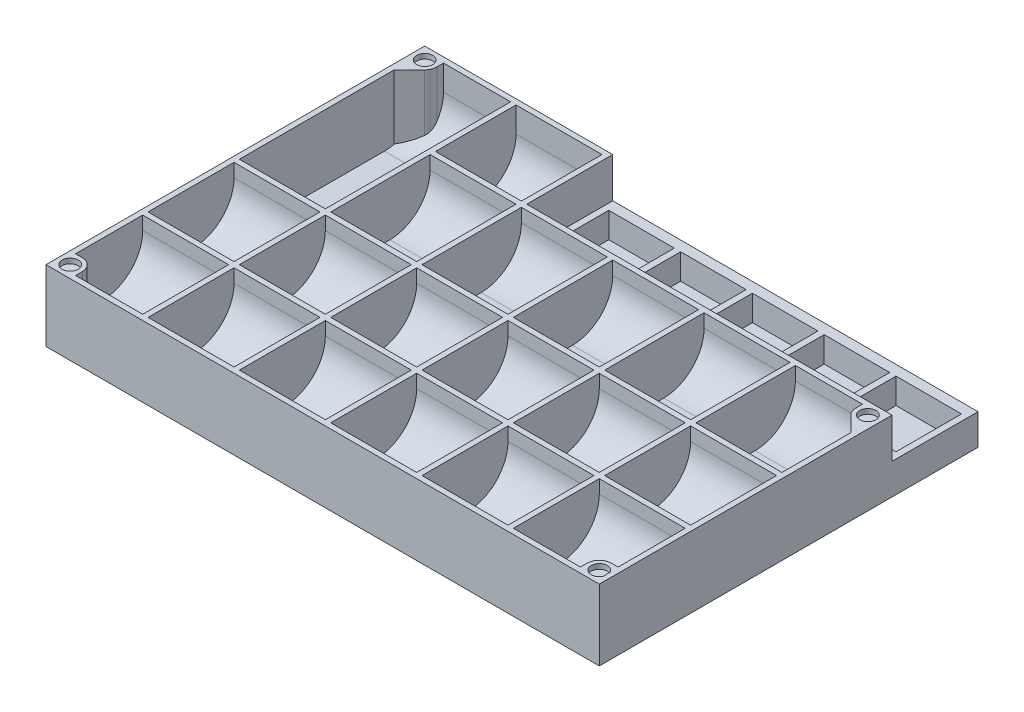
SolidWorks part; units mm, degrees
ref_plane "Front Plane" through (0, 0, 0) normal (0, 0, 1) x (1, 0, 0)
ref_plane "Top Plane" through (0, 0, 0) normal (0, 1, 0) x (1, 0, 0)
ref_plane "Right Plane" through (0, 0, 0) normal (1, 0, 0) x (0, 0, -1)
sketch "Sketch2" plane through (0, 0, 0) normal (1, 0, 0) x (0, 0, -1)
  line L0 (34, 26.4) -> (34, 32.7647)
  line L1 (0, 0) -> (141, 0)
  line L2 (0, 0) -> (0, 26.4)
  line L3 (0, 26.4) -> (141, 26.4)
  line L4 (141, 0) -> (141, 26.4)
  line L5 (2, 26.4) -> (34, 26.4)
  line L6 (2, 26.4) -> (2, 6.4)
  line L7 (2, 6.4) -> (19, 6.4)
  line L8 (34, 26.4) -> (34, 21.4)
  line L9 (36, 26.4) -> (68, 26.4)
  line L10 (36, 26.4) -> (36, 6.4)
  line L11 (36, 6.4) -> (53, 6.4)
  line L12 (68, 26.4) -> (68, 21.4)
  line L13 (70, 26.4) -> (107, 26.4)
  line L14 (70, 26.4) -> (70, 6.4)
  line L15 (70, 6.4) -> (92, 6.4)
  line L16 (107, 26.4) -> (107, 21.4)
  line L17 (109, 26.4) -> (139, 26.4)
  line L18 (109, 26.4) -> (109, 2)
  line L19 (109, 2) -> (124, 2)
  line L20 (139, 26.4) -> (139, 17)
  line L21 (70, 6.4) -> (70, 0)
  arc A0 (19, 6.4) -> (34, 21.4) centre (19, 21.4) ccw
  arc A1 (68, 21.4) -> (53, 6.4) centre (53, 21.4) cw
  arc A2 (107, 21.4) -> (92, 6.4) centre (92, 21.4) cw
  arc A3 (139, 17) -> (124, 2) centre (124, 17) cw
  dimension "D12" = 15
  dimension "D13" = 15
  dimension "D14" = 15
  dimension "D15" = 15
  dimension "D1" = 141
  dimension "D2" = 26.4
  dimension "D3" = 32
  dimension "D4" = 20
  dimension "D5" = 2
  dimension "D6" = 2
  dimension "D7" = 2
  dimension "D8" = 2
  dimension "D9" = 2
  dimension "D10" = 32
  dimension "D11" = 37
  dimension "D16" = 2
extrude "Boss-Extrude2" add sketch "Sketch2" against normal blind 2 contours L12 A1 L11 L10 L3 L8 A0 L7 L6 L2 L1 L21 L14 | L20 A3 L19 L18 L3 L16 A2 L15 L21 L1 L4 | A2 L16 L3 L14 L15 | A3 L20 L3 L18 L19 | A1 L12 L3 L10 L11 | L7 A0 L8 L3 L6 region at (0, 13.2, -0.7481) region at (0, 5.8938, -106.3105) region at (0, 16.8642, -87.4425) region at (0, 16.9426, -16.9678) region at (0, 14.825, -123.1773) region at (0, 16.9426, -50.9678)
extrude "Boss-Extrude3" add sketch "Sketch2<5>" against normal blind 34 contours L12 A1 L11 L10 L3 L8 A0 L7 L6 L2 L1 L21 L14 region at (0, 13.2, -0.7481)
sketch "Sketch2<5>" plane through (0, 0, 0) normal (1, 0, 0) x (0, 0, -1) same geometry as "Sketch2"
extrude "Boss-Extrude5" add sketch "Sketch2<9>" along normal blind 32 contours L12 A1 L11 L10 L3 L8 A0 L7 L6 L2 L1 L21 L14 | L20 A3 L19 L18 L3 L16 A2 L15 L21 L1 L4 region at (0, 13.2, -0.7481) region at (0, 5.8938, -106.3105)
sketch "Sketch2<9>" plane through (0, 0, 0) normal (1, 0, 0) x (0, 0, -1) same geometry as "Sketch2"
extrude "Boss-Extrude6" add sketch "Sketch2<10>" along normal blind 2 from offset 32 contours L12 A1 L11 L10 L3 L8 A0 L7 L6 L2 L1 L21 L14 | L20 A3 L19 L18 L3 L16 A2 L15 L21 L1 L4 | A3 L20 L3 L18 L19 | A2 L16 L3 L14 L15 | A1 L12 L3 L10 L11 | L7 A0 L8 L3 L6 region at (0, 13.2, -0.7481) region at (0, 5.8938, -106.3105) region at (0, 16.8642, -87.4425) region at (0, 16.9426, -16.9678) region at (0, 14.825, -123.1773) region at (0, 16.9426, -50.9678)
sketch "Sketch2<10>" plane through (0, 0, 0) normal (1, 0, 0) x (0, 0, -1) same geometry as "Sketch2"
extrude "Boss-Extrude7" add sketch "Sketch2<11>" along normal blind 32 from offset 34 contours L12 A1 L11 L10 L3 L8 A0 L7 L6 L2 L1 L21 L14 | L20 A3 L19 L18 L3 L16 A2 L15 L21 L1 L4 | A3 L20 L3 L18 L19 region at (0, 13.2, -0.7481) region at (0, 5.8938, -106.3105) region at (0, 14.825, -123.1773)
sketch "Sketch2<11>" plane through (0, 0, 0) normal (1, 0, 0) x (0, 0, -1) same geometry as "Sketch2"
extrude "Boss-Extrude8" add sketch "Sketch2<12>" along normal blind 2 from offset 66 contours L12 A1 L11 L10 L3 L8 A0 L7 L6 L2 L1 L21 L14 | L20 A3 L19 L18 L3 L16 A2 L15 L21 L1 L4 | A3 L20 L3 L18 L19 | A2 L16 L3 L14 L15 | A1 L12 L3 L10 L11 | L7 A0 L8 L3 L6 region at (0, 13.2, -0.7481) region at (0, 5.8938, -106.3105) region at (0, 16.8642, -87.4425) region at (0, 16.9426, -16.9678) region at (0, 14.825, -123.1773) region at (0, 16.9426, -50.9678)
sketch "Sketch2<12>" plane through (0, 0, 0) normal (1, 0, 0) x (0, 0, -1) same geometry as "Sketch2"
extrude "Boss-Extrude9" add sketch "Sketch2<13>" along normal blind 32 from offset 68 contours L12 A1 L11 L10 L3 L8 A0 L7 L6 L2 L1 L21 L14 | L20 A3 L19 L18 L3 L16 A2 L15 L21 L1 L4 | A3 L20 L3 L18 L19 region at (0, 13.2, -0.7481) region at (0, 5.8938, -106.3105) region at (0, 14.825, -123.1773)
sketch "Sketch2<13>" plane through (0, 0, 0) normal (1, 0, 0) x (0, 0, -1) same geometry as "Sketch2"
extrude "Boss-Extrude10" add sketch "Sketch2<14>" along normal blind 2 from offset 100 contours L12 A1 L11 L10 L3 L8 A0 L7 L6 L2 L1 L21 L14 | L7 A0 L8 L3 L6 | A1 L12 L3 L10 L11 | A2 L16 L3 L14 L15 | L20 A3 L19 L18 L3 L16 A2 L15 L21 L1 L4 | A3 L20 L3 L18 L19 region at (0, 13.2, -0.7481) region at (0, 5.8938, -106.3105) region at (0, 16.8642, -87.4425) region at (0, 16.9426, -16.9678) region at (0, 14.825, -123.1773) region at (0, 16.9426, -50.9678)
sketch "Sketch2<14>" plane through (0, 0, 0) normal (1, 0, 0) x (0, 0, -1) same geometry as "Sketch2"
extrude "Boss-Extrude11" add sketch "Sketch2<16>" along normal blind 32 from offset 102 contours L12 A1 L11 L10 L3 L8 A0 L7 L6 L2 L1 L21 L14 | L20 A3 L19 L18 L3 L16 A2 L15 L21 L1 L4 | A3 L20 L3 L18 L19 region at (0, 13.2, -0.7481) region at (0, 5.8938, -106.3105) region at (0, 14.825, -123.1773)
sketch "Sketch2<16>" plane through (0, 0, 0) normal (1, 0, 0) x (0, 0, -1) same geometry as "Sketch2"
extrude "Boss-Extrude12" add sketch "Sketch2<17>" along normal blind 2 from offset 134 contours L7 A0 L8 L3 L6 | L12 A1 L11 L10 L3 L8 A0 L7 L6 L2 L1 L21 L14 | A1 L12 L3 L10 L11 | L20 A3 L19 L18 L3 L16 A2 L15 L21 L1 L4 | A3 L20 L3 L18 L19 | A2 L16 L3 L14 L15 region at (0, 13.2, -0.7481) region at (0, 5.8938, -106.3105) region at (0, 16.8642, -87.4425) region at (0, 16.9426, -16.9678) region at (0, 14.825, -123.1773) region at (0, 16.9426, -50.9678)
sketch "Sketch2<17>" plane through (0, 0, 0) normal (1, 0, 0) x (0, 0, -1) same geometry as "Sketch2"
extrude "Boss-Extrude13" add sketch "Sketch2<18>" against normal blind 2 from offset 34 contours L20 A3 L19 L18 L3 L16 A2 L15 L21 L1 L4 | A3 L20 L3 L18 L19 | A2 L16 L3 L14 L15 | A1 L12 L3 L10 L11 | L12 A1 L11 L10 L3 L8 A0 L7 L6 L2 L1 L21 L14 | L7 A0 L8 L3 L6 region at (0, 13.2, -0.7481) region at (0, 5.8938, -106.3105) region at (0, 16.8642, -87.4425) region at (0, 16.9426, -16.9678) region at (0, 14.825, -123.1773) region at (0, 16.9426, -50.9678) offset against normal yes
sketch "Sketch2<18>" plane through (0, 0, 0) normal (1, 0, 0) x (0, 0, -1) same geometry as "Sketch2"
extrude "Boss-Extrude14" add sketch "Sketch2<19>" along normal blind 32 from offset 136 contours L12 A1 L11 L10 L3 L8 A0 L7 L6 L2 L1 L21 L14 | L20 A3 L19 L18 L3 L16 A2 L15 L21 L1 L4 | A3 L20 L3 L18 L19 region at (0, 13.2, -0.7481) region at (0, 5.8938, -106.3105) region at (0, 14.825, -123.1773)
sketch "Sketch2<19>" plane through (0, 0, 0) normal (1, 0, 0) x (0, 0, -1) same geometry as "Sketch2"
extrude "Boss-Extrude15" add sketch "Sketch2<20>" along normal blind 2 from offset 168 contours L12 A1 L11 L10 L3 L8 A0 L7 L6 L2 L1 L21 L14 | A1 L12 L3 L10 L11 | L7 A0 L8 L3 L6 | A2 L16 L3 L14 L15 | L20 A3 L19 L18 L3 L16 A2 L15 L21 L1 L4 | A3 L20 L3 L18 L19 region at (0, 13.2, -0.7481) region at (0, 5.8938, -106.3105) region at (0, 16.8642, -87.4425) region at (0, 16.9426, -16.9678) region at (0, 14.825, -123.1773) region at (0, 16.9426, -50.9678)
sketch "Sketch2<20>" plane through (0, 0, 0) normal (1, 0, 0) x (0, 0, -1) same geometry as "Sketch2"
sketch "Sketch3" plane through (-2, 0, 0) normal (-1, 0, 0) x (0, 0, 1)
  line L1 (-141, 26.4) -> (-70, 26.4)
  line L2 (-141, 26.4) -> (-141, 0)
  line L3 (-141, 0) -> (-70, 0)
  line L4 (-70, 26.4) -> (-70, 0)
  line L5 (-139, 26.4) -> (-70, 26.4)
  line L6 (-139, 26.4) -> (-139, 17)
  line L7 (-124, 2) -> (-70, 2)
  line L8 (-70, 26.4) -> (-70, 2)
  arc A0 (-124, 2) -> (-139, 17) centre (-124, 17) cw
  line M9 (-70, 0) -> (-70, 26.4)
  line M11 (-141, 26.4) -> (-141, 0)
  line M12 (-141, 0) -> (-70, 0)
  dimension "D3" = 15
  dimension "D1" = 2
  dimension "D2" = 2
extrude "Boss-Extrude16" add sketch "Sketch3" along normal blind 32 contours L7 A0 L6 L1 M11 M12 M9 region at (-2, 25.6425, -140)
sketch "Sketch4" plane through (0, 26.4, 0) normal (0, 1, 0) x (1, 0, 0)
  line L1 (34, 109) -> (170, 109)
  line L2 (34, 109) -> (34, 141)
  line L3 (34, 141) -> (170, 141)
  line L4 (170, 109) -> (170, 141)
  line L5 (34, 70) -> (34, 107) construction
  line L6 (32, 109) -> (0, 109) construction
  line L8 (36.3333, 125) -> (34, 125)
  line L9 (36.3333, 137.2) -> (60.7333, 137.2)
  line L10 (36.3333, 137.2) -> (36.3333, 112.8)
  line L11 (36.3333, 112.8) -> (60.7333, 112.8)
  line L12 (60.7333, 137.2) -> (60.7333, 112.8)
  line L13 (63.0667, 137.2) -> (87.4667, 137.2)
  line L14 (63.0667, 137.2) -> (63.0667, 112.8)
  line L15 (63.0667, 112.8) -> (87.4667, 112.8)
  line L16 (87.4667, 137.2) -> (87.4667, 112.8)
  line L17 (89.8, 137.2) -> (114.2, 137.2)
  line L18 (89.8, 137.2) -> (89.8, 112.8)
  line L19 (89.8, 112.8) -> (114.2, 112.8)
  line L20 (114.2, 137.2) -> (114.2, 112.8)
  line L21 (116.5333, 137.2) -> (140.9333, 137.2)
  line L22 (116.5333, 137.2) -> (116.5333, 112.8)
  line L23 (116.5333, 112.8) -> (140.9333, 112.8)
  line L24 (140.9333, 137.2) -> (140.9333, 112.8)
  line L25 (143.2667, 137.2) -> (167.6667, 137.2)
  line L26 (143.2667, 137.2) -> (143.2667, 112.8)
  line L27 (143.2667, 112.8) -> (167.6667, 112.8)
  line L28 (167.6667, 137.2) -> (167.6667, 112.8)
  line L29 (60.7333, 125) -> (63.0667, 125)
  line L30 (87.4667, 125) -> (89.8, 125)
  line L31 (114.2, 125) -> (116.5333, 125)
  line L32 (140.9333, 125) -> (143.2667, 125)
  line L33 (167.6667, 125) -> (170, 125)
  dimension "D1" = 24.4
  dimension "D2" = 24.4
extrude "Cut-Extrude1" cut sketch "Sketch4" against normal blind 14.9 contours L28 L33 L4 L3 L2 L8 L10 L9 L12 L29 L14 L13 L16 L30 L18 L17 L20 L31 L22 L21 L24 L32 L26 L25 | L33 L28 L27 L26 L32 L24 L23 L22 L31 L20 L19 L18 L30 L16 L15 L14 L29 L12 L11 L10 L8 L2 L1 L4 | L12 L9 L10 L11 | L16 L13 L14 L15 | L20 L17 L18 L19 | L24 L21 L22 L23 | L28 L25 L26 L27 region at (35.3694, 26.4, -117) region at (35.3694, 26.4, -133) region at (48.5333, 26.4, -125) region at (155.4667, 26.4, -125) region at (75.2667, 26.4, -125) region at (128.7333, 26.4, -125) region at (102, 26.4, -125)
extrude "Cut-Extrude2" cut sketch "Sketch4<4>" against normal blind 24.4 contours L12 L9 L10 L11 | L16 L13 L14 L15 | L20 L17 L18 L19 | L24 L21 L22 L23 | L28 L25 L26 L27 region at (48.5333, 26.4, -125) region at (155.4667, 26.4, -125) region at (75.2667, 26.4, -125) region at (128.7333, 26.4, -125) region at (102, 26.4, -125)
sketch "Sketch4<4>" plane through (0, 26.4, 0) normal (0, 1, 0) x (1, 0, 0) same geometry as "Sketch4"
sketch "Sketch6" plane through (0, 26.4, 0) normal (0, 1, 0) x (1, 0, 0)
  line L0 (-36, 0) -> (-36, 141) construction
  line L1 (-36, 0) -> (170, 0) construction
  line L2 (-34, 9) -> (-31.5, 9)
  line L3 (-34, 2) -> (-34, 34) construction
  line L4 (-27, 4.5) -> (-27, 2)
  line L5 (-34, 2) -> (-2, 2) construction
  line L6 (170, 0) -> (170, 109) construction
  line L7 (161, 2) -> (161, 4.5)
  line L8 (168, 2) -> (136, 2) construction
  line L9 (165.5, 9) -> (168, 9)
  line L10 (168, 2) -> (168, 34) construction
  line L11 (34, 109) -> (170, 109) construction
  line L12 (-36, 141) -> (34, 141) construction
  line L13 (-27, 139) -> (-27, 136.5)
  line L14 (-34, 139) -> (-2, 139) construction
  line L15 (-31.5, 132) -> (-34, 132)
  line L16 (-34, 70) -> (-34, 139) construction
  line L17 (-28.318, 133.318) -> (-34, 127.636)
  line L18 (-34, 127.636) -> (-35.3113, 140.1685)
  line L19 (-35.3113, 140.1685) -> (-27, 139)
  line L20 (-34, 9) -> (-35.6027, 0.9916)
  line L21 (-35.6027, 0.9916) -> (-27, 2)
  line L22 (161, 2) -> (168.3395, 0.9681)
  line L23 (168.3395, 0.9681) -> (168, 9)
  line L24 (161, 107) -> (161, 104.5)
  line L25 (168, 107) -> (136, 107) construction
  line L26 (165.5, 100) -> (168, 100)
  line L27 (168, 70) -> (168, 107) construction
  line L28 (162.318, 101.318) -> (168, 95.636)
  line L29 (168, 95.636) -> (169.4662, 108.4662)
  line L30 (169.4662, 108.4662) -> (161, 107)
  circle A0 centre (-31.5, 4.5) radius 3
  arc A1 (-27, 4.5) -> (-31.5, 9) centre (-31.5, 4.5) ccw
  circle A2 centre (165.5, 4.5) radius 3
  arc A3 (165.5, 9) -> (161, 4.5) centre (165.5, 4.5) ccw
  circle A4 centre (-31.5, 136.5) radius 3
  arc A5 (-31.5, 132) -> (-27, 136.5) centre (-31.5, 136.5) ccw
  circle A7 centre (165.5, 104.5) radius 3
  arc A8 (161, 104.5) -> (165.5, 100) centre (165.5, 104.5) ccw
  dimension "D1" = 4.5
  dimension "D3" = 6
  dimension "D4" = 4.5
  dimension "D5" = 0
  dimension "D6" = 4.5
  dimension "D10" = 4.5
  dimension "D8" = 4.5
  dimension "D11" = 0
  dimension "D14" = 4.5
  dimension "D2" = 4.5
  dimension "D7" = 4.5
  dimension "D9" = 4.5
  dimension "D12" = 4.5
  dimension "D13" = 4.5
extrude "Boss-Extrude17" add sketch "Sketch6" against normal blind 24.4 contours L4 A1 L2 L20 L21 A0 | A0 | L9 A3 L7 L22 L23 A2 | A2 | A5 L13 L19 L18 L17 A4 | A4 | A7 | L24 A8 L28 L29 L30 A7 region at (-32.75, 26.4, -8.8825) region at (161.1088, 26.4, -3.25) region at (165.4431, 26.4, -4.4976) region at (-27.1504, 26.4, -137.75) region at (165.2593, 26.4, -107.5816) region at (-31.5, 26.4, -4.5) region at (-31.5, 26.4, -136.5) region at (165.5, 26.4, -104.5)
extrude "Cut-Extrude3" cut sketch "Sketch6<3>" against normal blind 1.85 contours A4 | A0 | A2 | A7 region at (165.4431, 26.4, -4.4976) region at (-31.5, 26.4, -4.5) region at (-31.5, 26.4, -136.5) region at (165.5, 26.4, -104.5)
sketch "Sketch6<3>" plane through (0, 26.4, 0) normal (0, 1, 0) x (1, 0, 0) same geometry as "Sketch6"
